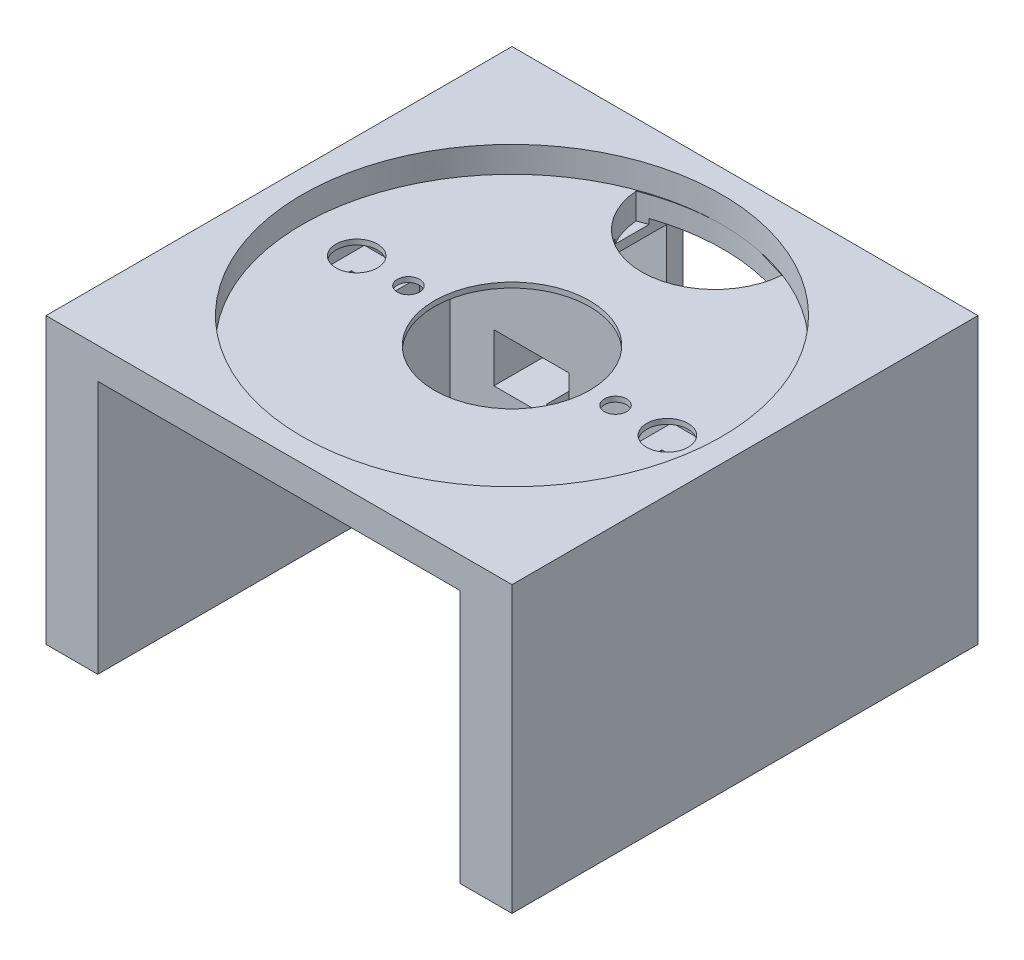
SolidWorks part; units mm, degrees
ref_plane "Front Plane" through (0, 0, 0) normal (0, 0, 1) x (1, 0, 0)
ref_plane "Top Plane" through (0, 0, 0) normal (0, 1, 0) x (1, 0, 0)
ref_plane "Right Plane" through (0, 0, 0) normal (1, 0, 0) x (0, 0, -1)
sketch "Sketch1" plane through (0, 0, 0) normal (0, 1, 0) x (1, 0, 0)
  line L2 (0, -45) -> (-45, -45)
  line L3 (-45, -45) -> (-45, 45)
  line L4 (-45, 45) -> (0, 45)
  line L5 (0, 45) -> (45, 45)
  line L6 (45, 45) -> (45, -45)
  line L7 (45, -45) -> (0, -45)
extrude "Boss-Extrude1" add sketch "Sketch1" along normal blind 10
sketch "Sketch2" plane through (0, 10, 0) normal (0, 1, 0) x (1, 0, 0)
  circle A0 centre (0, 0) radius 40.5
extrude "Cut-Extrude1" cut sketch "Sketch2" against normal blind 5 contours A0
sketch "Sketch4" plane through (0, 5, 0) normal (0, 1, 0) x (1, 0, 0)
  circle A2 centre (-20, 0) radius 2.15
  circle A3 centre (20, 0) radius 2.15
extrude "Cut-Extrude2" cut sketch "Sketch4" against normal blind 2
sketch "Sketch5" plane through (0, 5, 0) normal (0, 1, 0) x (1, 0, 0)
  circle A0 centre (0, 0) radius 15
extrude "Cut-Extrude3" cut sketch "Sketch5" against normal through all
sketch "Sketch7" plane through (0, 5, 0) normal (0, 1, 0) x (1, 0, 0)
  arc A0 (-13.8415, 37.8005) -> (14.3106, 37.8005) centre (0.2345, 38.9392) ccw
  arc A1 (-13.8415, 37.8005) -> (14.3106, 37.8005) centre (0.2345, 2.5037) cw
extrude "Cut-Extrude4" cut sketch "Sketch7" against normal blind 66 contours A0 A1
sketch "Sketch8" plane through (0, 0, 0) normal (0, -1, 0) x (1, 0, 0)
  line L0 (-45, 45) -> (45, 45)
  line L1 (45, 45) -> (45, -45)
  line L2 (45, -45) -> (-45, -45)
  line L3 (-45, -45) -> (-45, 45)
extrude "Boss-Extrude2" add sketch "Sketch8" along normal blind 45
sketch "Sketch9" plane through (0, 0, 45) normal (0, 0, 1) x (1, 0, 0)
  line L0 (-45, -45) -> (-35, -45)
  line L1 (45, -45) -> (-45, -45) construction
  line L2 (-35, -45) -> (-35, 4)
  line L3 (-35, 4) -> (35, 4)
  line L4 (35, 4) -> (35, -45)
  line L5 (35, -45) -> (-35, -45)
extrude "Cut-Extrude5" cut sketch "Sketch9" against normal blind 68 contours L2 L3 L4 L5
sketch "Sketch10" plane through (0, 0, -45) normal (0, 0, -1) x (-1, 0, 0)
  line L8 (0, 10) -> (0, -45) construction
  line L9 (-45, 10) -> (45, 10) construction
  line L13 (45, -45) -> (-45, -45) construction
  line L14 (-45, -17.5) -> (45, -17.5) construction
  line L15 (-45, 10) -> (-45, -45) construction
  line L16 (45, 10) -> (45, -45) construction
  line L29 (-12, -21) -> (-12, -25)
  line L36 (-12, -25) -> (-18, -25)
  line L37 (-12, -21) -> (-12, -2)
  line L39 (-12, -2) -> (-12, 1)
  line L40 (-12, 1) -> (12, 1)
  line L41 (12, -25) -> (12, 1)
  line L42 (12, -25) -> (18.3379, -25)
  line L43 (-18, -25) -> (-18, -37)
  line L44 (18.3379, -25) -> (18.3379, -37)
  line L45 (18.3379, -37) -> (-18, -37)
extrude "Cut-Extrude7" cut sketch "Sketch10" against normal blind 20
sketch "Sketch12" plane through (0, 0, -45) normal (0, 0, -1) x (-1, 0, 0)
  text T0 "ProtoPill\r\nDispenser\r\nTester"
extrude "Cut-Extrude9" cut sketch "Sketch12" against normal blind 4
sketch "Sketch17" plane through (0, -37, 0) normal (0, 1, 0) x (1, 0, 0)
  line L0 (-0.1689, 24) -> (-0.1689, 45) construction
  line L2 (18, 45) -> (-18.3379, 45) construction
  line L3 (18, 35) -> (-18.3379, 35) construction
  line L4 (18, 25) -> (18, 45) construction
  line L5 (-18.3379, 25) -> (-18.3379, 45) construction
  line L6 (11.8311, 35) -> (11.8311, 26.5)
  line L7 (-12.1689, 35) -> (-12.1689, 42.5)
  line L8 (-12.1689, 35) -> (-12.1689, 26.5)
  line L9 (11.8311, 35) -> (11.8311, 42.5)
  line L10 (11.8311, 26.5) -> (-12.1689, 26.5)
  line L11 (-12.1689, 42.5) -> (11.8311, 42.5)
extrude "Cut-Extrude12" cut sketch "Sketch17" against normal blind 3
sketch "Sketch18" plane through (0, -40, 0) normal (0, 1, 0) x (1, 0, 0)
  circle A0 centre (-0.1689, 32.5) radius 11.15
  dimension "D1" = 22.3
extrude "Cut-Extrude13" cut sketch "Sketch18" against normal blind 4.66
sketch "Sketch20" plane through (-12, 0, 0) normal (1, 0, 0) x (0, 0, -1)
  line L0 (35, -25) -> (35, 0) construction
  line L1 (25, -25) -> (45, -25) construction
  line L2 (38.4803, 0) -> (31.8859, 0) construction
  line L10 (28.17, -1.7) -> (41.83, -1.7)
  line L13 (41.83, -1.7) -> (41.83, -26.5)
  line L14 (28.17, -26.5) -> (41.83, -26.5)
  line L15 (28.17, -26.5) -> (28.17, -1.7)
extrude "Cut-Extrude14" cut sketch "Sketch20" against normal blind 14.5
sketch "Sketch22" plane through (-26.5, 0, 0) normal (1, 0, 0) x (0, 0, -1)
  line L0 (35, -26.5) -> (35, -1.7) construction
  line L3 (28.17, -17.05) -> (41.83, -17.05) construction
  line L6 (28.17, -26.5) -> (41.83, -26.5) construction
  line L7 (41.83, -1.7) -> (28.17, -1.7) construction
  line L8 (28.17, -1.7) -> (28.17, -26.5) construction
  line L9 (41.83, -26.5) -> (41.83, -1.7) construction
  circle A0 centre (35, -17.05) radius 1.45
  dimension "D1" = 2.9
extrude "Boss-Extrude3" add sketch "Sketch22" along normal blind 9
sketch "Sketch24" plane through (12, 0, 0) normal (-1, 0, 0) x (0, 0, 1)
  line L0 (-41.83, -1.7) -> (-28.17, -1.7) construction
  line L1 (-28.17, -1.7) -> (-28.17, -26.5)
  line L4 (-41.83, -1.7) -> (-28.17, -1.7)
  line L13 (-41.83, -1.7) -> (-41.83, -26.5)
  line L14 (-41.83, -26.5) -> (-28.17, -26.5)
  circle A0 centre (-35, -17.05) radius 1.45 construction
  circle A1 centre (-35, -17.05) radius 1.45
  dimension "D2" = 2.9
  dimension "D1" = 13.66
extrude "Cut-Extrude16" cut sketch "Sketch24" against normal blind 14.5
sketch "Sketch40" plane through (0, 0, -28.17) normal (0, 0, -1) x (-1, 0, 0)
  line L0 (-26.5, -26.5) -> (-18, -26.5)
  line L3 (-12, -25) -> (-12, -17.0937)
  line L4 (-12, -25) -> (-12, -1.7) construction
  line L5 (-12, -17.0937) -> (-26.5, -17.0937)
  line L6 (-26.5, -26.5) -> (-26.5, -1.7) construction
  line L7 (-26.5, -17.0937) -> (-26.5, -26.5)
  line L8 (0, 0) -> (0, -35.411) construction
  line L9 (26.5, -17.0937) -> (26.5, -26.5)
  line L10 (12, -17.0937) -> (26.5, -17.0937)
  line L11 (12, -25) -> (12, -17.0937)
  line L14 (26.5, -26.5) -> (18, -26.5)
  line L15 (-12, -25) -> (-12, -26.5)
  line L16 (-12, -26.5) -> (-18, -26.5)
  line L17 (12, -25) -> (12, -26.5)
  line L18 (12, -26.5) -> (18, -26.5)
extrude "Cut-Extrude29" cut sketch "Sketch40" against normal blind 10
sketch "Sketch32" plane through (0, 0, -23) normal (0, 0, 1) x (1, 0, 0)
  line L0 (-6.0061, -40) -> (-6.0061, -44.66)
  line L9 (-0.1689, -40) -> (-0.1689, -44.66) construction
  line L10 (-5.1007, -40) -> (4.7628, -40) construction
  line L11 (10.9811, -44.66) -> (-11.3189, -44.66) construction
  line L25 (10.9711, -40) -> (5.6682, -40)
  line L26 (-11.3089, -40) -> (-11.3089, -44.66)
  line L27 (-11.3089, -44.66) -> (-6.0061, -44.66)
  line L28 (-11.3089, -40) -> (-6.0061, -40)
  line L29 (10.9711, -44.66) -> (5.6682, -44.66)
  line L30 (10.9711, -40) -> (10.9711, -44.66)
  line L31 (5.6682, -40) -> (5.6682, -44.66)
extrude "Cut-Extrude21" cut sketch "Sketch32" against normal blind 10
sketch "Sketch33" plane through (0, 5, 0) normal (0, 1, 0) x (1, 0, 0)
  circle A0 centre (-29.9677, -0.0225) radius 4
  circle A1 centre (30.0323, -0.0225) radius 4
extrude "Cut-Extrude22" cut sketch "Sketch33" against normal blind 10
sketch "Sketch41" plane through (0, 4, 0) normal (0, -1, 0) x (1, 0, 0)
sketch "Sketch42" plane through (-35, 0, 0) normal (1, 0, 0) x (0, 0, -1)
  line L0 (0, 4) -> (0, 1) construction
  line L1 (23, 4) -> (-45, 4) construction
  line L2 (0, 1) -> (-6.5, 1)
  line L3 (0, 1) -> (6.5, 1)
  line L4 (6.5, 1) -> (6.5, -3)
  line L5 (6.5, -3) -> (-6.5, -3)
  line L6 (-6.5, -3) -> (-6.5, 1)
  dimension "D1" = 3
extrude "Boss-Extrude5" add sketch "Sketch42" along normal blind 10.61
sketch "Sketch45" plane through (35, 0, 0) normal (-1, 0, 0) x (0, 0, 1)
  line L12 (6.5, 1) -> (-6.5, 1)
  line L13 (6.5, -3) -> (6.5, 1)
  line L14 (-6.5, -3) -> (6.5, -3)
  line L15 (-6.5, 1) -> (-6.5, -3)
  line L16 (6.5, 1) -> (-6.5, 1)
  line L17 (6.5, -3) -> (6.5, 1)
  line L18 (-6.5, -3) -> (6.5, -3)
  line L19 (-6.5, 1) -> (-6.5, -3)
  dimension "D2" = 0
extrude "Boss-Extrude6" add sketch "Sketch45" along normal blind 10.61
sketch "Sketch43" plane through (0, 0, 6.5) normal (0, 0, 1) x (1, 0, 0)
  line L0 (35, 1) -> (29.9677, 1) construction
  line L1 (-24.39, 1) -> (-35, 1) construction
  line L2 (32.0227, -0.9) -> (27.9127, -0.9)
  line L8 (32.0227, 1) -> (27.9127, 1)
  line L9 (27.9127, -0.9) -> (27.9127, 1)
  line L11 (-32.0227, 1) -> (-32.0227, -0.9)
  line L13 (-27.9127, -0.9) -> (-27.9127, 1)
  line L15 (-32.0227, 1) -> (-27.9127, 1)
  line L16 (-32.0227, -0.9) -> (-27.9127, -0.9)
  line L17 (32.0227, 1) -> (32.0227, -0.9)
  line L18 (-35, 1) -> (-29.9677, 1) construction
  line L19 (0, 3.2679) -> (0, -14.8527) construction
extrude "Cut-Extrude30" cut sketch "Sketch43" against normal blind 7.5
